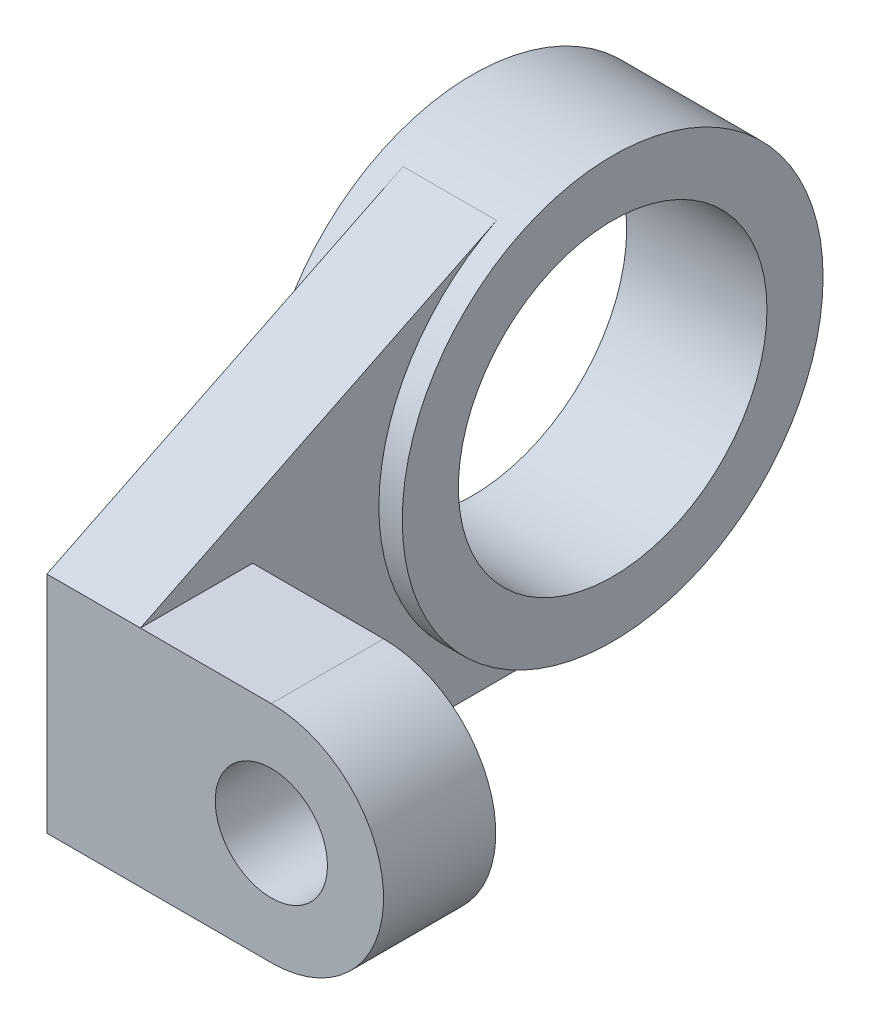
SolidWorks part; units mm, degrees
ref_plane "前基準面" through (0, 0, 0) normal (0, 0, 1) x (1, 0, 0)
ref_plane "上基準面" through (0, 0, 0) normal (0, 1, 0) x (1, 0, 0)
ref_plane "右基準面" through (0, 0, 0) normal (1, 0, 0) x (0, 0, -1)
sketch "草圖1" plane through (0, 0, 0) normal (1, 0, 0) x (0, 0, -1)
  line L0 (0, 0) -> (76.1686, 37.3945)
  line L1 (0, 0) -> (0, -48)
  line L2 (0, -48) -> (96, -48)
  circle A0 centre (96, -3) radius 33
  circle A1 centre (96, -3) radius 45
  dimension "D1" = 66
  dimension "D2" = 90
  dimension "D3" = 96
  dimension "D4" = 48
extrude "填料-伸長1" add sketch "草圖1" along normal mid plane 20 contours A1 L0 L1 L2 region at (0, -18.3387, -32.3373)
extrude "填料-伸長2" add sketch "草圖1<4>" along normal mid plane 30 contours A1 A0 region at (0, 34.1128, -119.1238)
sketch "草圖1<4>" plane through (0, 0, 0) normal (1, 0, 0) x (0, 0, -1) same geometry as "草圖1"
sketch "草圖2" plane through (0, 0, 0) normal (0, 0, 1) x (1, 0, 0)
  line L0 (10, 0) -> (38, 0)
  line L1 (10, -48) -> (38, -48)
  line L2 (-10, 0) -> (-10, -48) construction
  arc A0 (38, -48) -> (38, 0) centre (38, -24) ccw
  circle A1 centre (38, -24) radius 12
  line M5 (10, -48) -> (10, 0)
  dimension "D1" = 48
  dimension "D2" = 24
extrude "填料-伸長3" add sketch "草圖2" against normal blind 24 contours L1 A0 L0 A1 M5 region at (24, -0.7077, 0)
